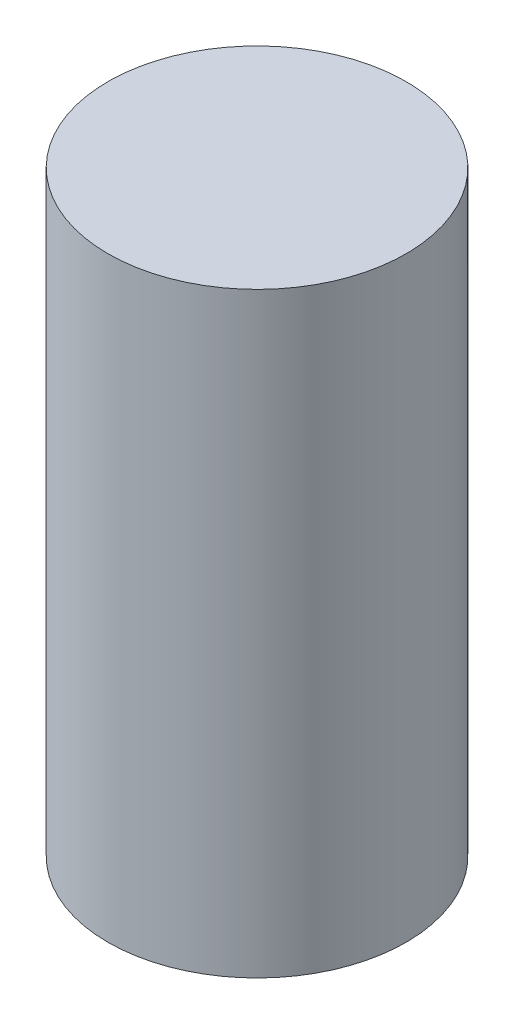
SolidWorks part; units mm, degrees
ref_plane "Front Plane" through (0, 0, 0) normal (0, 0, 1) x (1, 0, 0)
ref_plane "Top Plane" through (0, 0, 0) normal (0, 1, 0) x (1, 0, 0)
ref_plane "Right Plane" through (0, 0, 0) normal (1, 0, 0) x (0, 0, -1)
sketch "Sketch1" plane through (0, 0, 0) normal (0, 1, 0) x (1, 0, 0)
  circle A0 centre (0, 0) radius 2.5
  dimension "D1" = 5
extrude "Boss-Extrude1" add sketch "Sketch1" along normal blind 5 and the other way blind 5 contours A0
